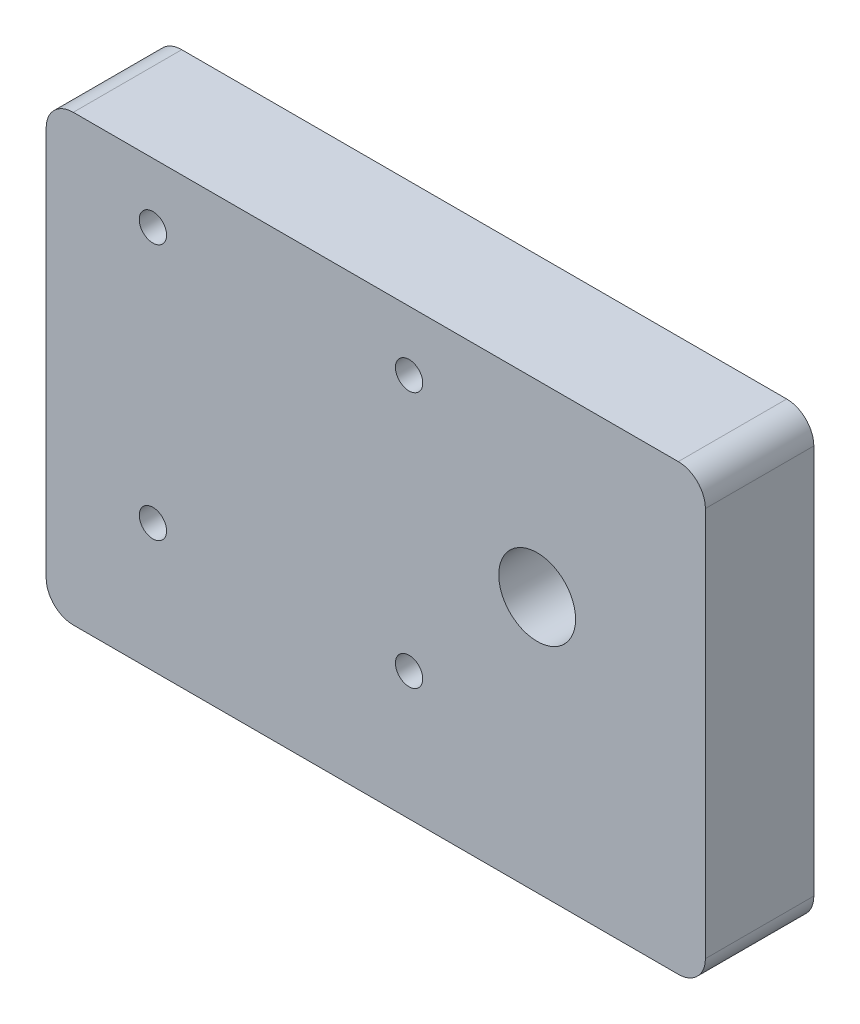
SolidWorks part; units mm, degrees
note: The reader was unsure of these and kept them because the rebuilt part matched: shared geometry of "Sketch1<5>".
ref_plane "Front Plane" through (0, 0, 0) normal (0, 0, 1) x (1, 0, 0)
ref_plane "Top Plane" through (0, 0, 0) normal (0, 1, 0) x (1, 0, 0)
ref_plane "Right Plane" through (0, 0, 0) normal (1, 0, 0) x (0, 0, -1)
sketch "Sketch1" plane through (0, 0, 0) normal (0, 0, 1) x (1, 0, 0)
  line L0 (22.5, 0) -> (22.5, -44) construction
  line L1 (0, 0) -> (48.3, 0)
  line L2 (0, 0) -> (0, -44)
  line L3 (0, -44) -> (48.3, -44)
  line L4 (48.3, 0) -> (48.3, -44) construction
  line L5 (22.5, -22) -> (52.5, -22) construction
  line L6 (48.3, 0) -> (59.5, 0)
  line L7 (59.5, 0) -> (59.5, -44)
  line L8 (59.5, -44) -> (48.3, -44)
  line L10 (59.5, 0) -> (72.2, 0)
  line L11 (59.5, 0) -> (59.5, -44)
  line L12 (59.5, -44) -> (72.2, -44)
  line L13 (72.2, 0) -> (72.2, -44)
  circle A0 centre (7.5, -37) radius 1.6
  circle A20 centre (37.5, -37) radius 1.6
  circle A21 centre (37.5, -7) radius 1.6
  circle A22 centre (7.5, -7) radius 1.6
  circle A24 centre (0, 0) radius 2.5 construction
  circle A25 centre (52.5, -22) radius 4.5
  point P19 (22.5, -22)
  dimension "D3" = 3.2
  dimension "D10" = 9
  dimension "D1" = 48.3
  dimension "D2" = 44
  dimension "D4" = 7.5
  dimension "D5" = 7
  dimension "D8" = 30
  dimension "D9" = 30
  dimension "D12" = 22.5
  dimension "D11" = 30
  dimension "D14" = 7
  dimension "D15" = 12.7
  dimension "D6" = 2
  dimension "D7" = 2
extrude "Boss-Extrude1" add sketch "Sketch1" along normal blind 12.7
sketch "Sketch2" plane through (0, 0, 12.7) normal (0, 0, 1) x (1, 0, 0)
  line L0 (72.2, -44) -> (0, -44) construction
  line L1 (0, -44) -> (72.2, -44)
  line L2 (0, -44) -> (0, -52)
  line L3 (0, -52) -> (72.2, -52)
  line L4 (72.2, -44) -> (72.2, -52)
  line L5 (0, 0) -> (-5, 0)
  line L6 (0, 0) -> (0, -52)
  line L7 (0, -52) -> (-5, -52)
  line L8 (-5, 0) -> (-5, -52)
  line L13 (72.2, 0) -> (72.2, -44) construction
  point P5 (67.7772, -44)
  point P6 (0, 0)
  point P10 (67.5, -44)
  dimension "D1" = 8
  dimension "D2" = 5
extrude "Boss-Extrude2" add sketch "Sketch2" against normal up to surface (12.7 mm away) up to face at (36.1, -22, 0)
extrude "Cut-Extrude3" cut sketch "Sketch1<5>" along normal through all contours A25 | A0 | A22 | A21 | A20
sketch "Sketch1<5>" plane through (0, 0, 0) normal (0, 0, 1) x (1, 0, 0) same geometry as "Sketch1"
fillet "Fillet1" radius 3.175 4 edges at (72.2, -52, 6.35) (-5, 0, 6.35) (-5, -52, 6.35) (72.2, 0, 6.35)
equation "\"D4@Sketch1\"=(\"D1@Sketch1\"-\"D9@Sketch1\")/2-1.65"
